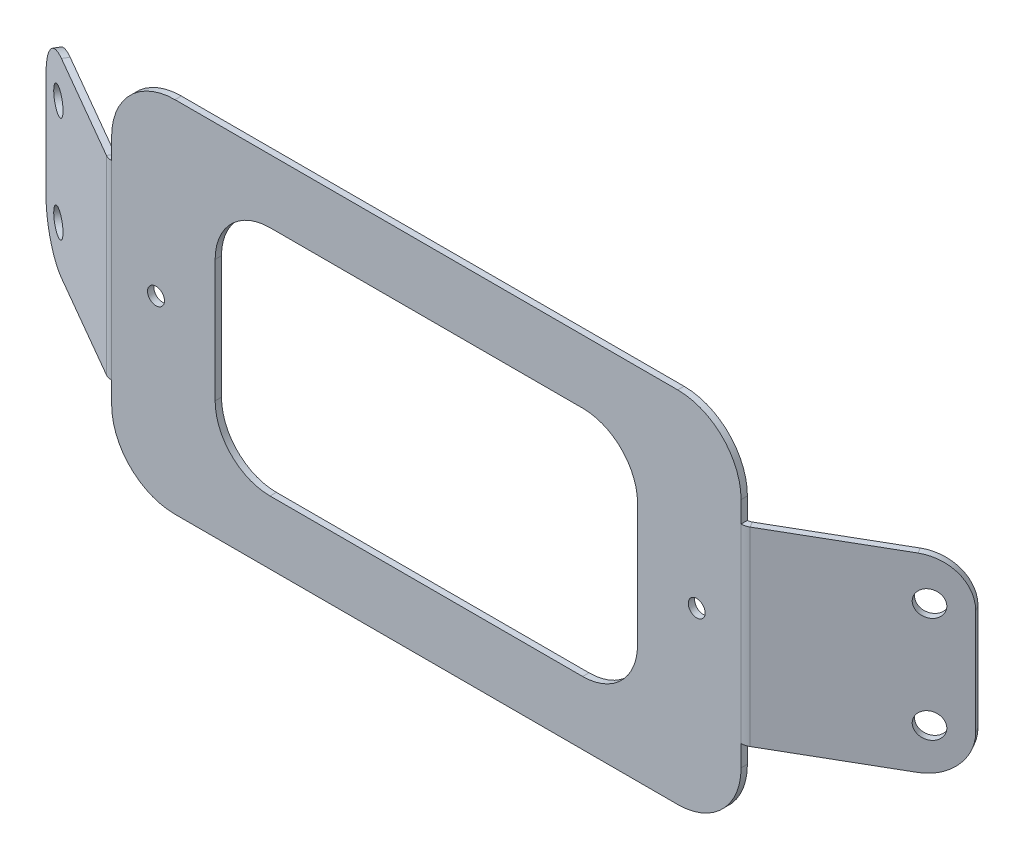
SolidWorks part; units mm, degrees
note: The reader was unsure of these and kept them because the rebuilt part matched: flange length of "Ребро-кромка1".
ref_plane "Спереди" through (0, 0, 0) normal (0, 0, 1) x (1, 0, 0)
ref_plane "Сверху" through (0, 0, 0) normal (0, 1, 0) x (1, 0, 0)
ref_plane "Справа" through (0, 0, 0) normal (1, 0, 0) x (0, 0, -1)
sketch "Sketch1" plane through (0, 0, 0) normal (0, 0, 1) x (1, 0, 0)
  line L1 (15, 0) -> (134, 0)
  line L2 (0, 15) -> (0, 70)
  line L3 (15, 85) -> (134, 85)
  line L4 (149, 15) -> (149, 70)
  line L9 (111.5, 15) -> (37.5, 15)
  line L10 (124.5, 28) -> (124.5, 57)
  line L11 (111.5, 70) -> (37.5, 70)
  line L12 (24.5, 28) -> (24.5, 57)
  arc A4 (37.5, 70) -> (24.5, 57) centre (37.5, 57) ccw
  arc A5 (37.5, 15) -> (24.5, 28) centre (37.5, 28) cw
  arc A6 (124.5, 57) -> (111.5, 70) centre (111.5, 57) ccw
  arc A7 (111.5, 15) -> (124.5, 28) centre (111.5, 28) ccw
  arc A8 (0, 70) -> (15, 85) centre (15, 70) cw
  arc A9 (15, 0) -> (0, 15) centre (15, 15) cw
  arc A10 (134, 85) -> (149, 70) centre (134, 70) cw
  arc A11 (134, 0) -> (149, 15) centre (134, 15) ccw
  point P13 (24.5, 15)
  point P16 (124.5, 70)
  point P19 (124.5, 15)
  point P22 (0, 85)
  point P25 (0, 0)
  point P30 (149, 0)
  dimension "D4" = 100
  dimension "D7" = 13
  dimension "D8" = 15
  dimension "D1" = 149
  dimension "D2" = 85
  dimension "D5" = 24.5
  dimension "D3" = 55
  dimension "D6" = 15
base flange "Base-Flange1" sketch "Sketch1" thickness 1.5 reverse thickness direction no parameters "D1"=1.85
edge flange "Ребро-кромка1" sketch "Sketch10" flange profiles "Sketch10", "Sketch11" flange angle 150 flange length 40 flange position bend outside bend radius 1.85 thickness 1.5 relief rectangular parameters "D6"=10, "D8"=1
sketch "Sketch10" plane through (0, 0, -1.5) normal (0.5, 0, -0.866) x (0, -1, 0)
  line L3 (-65, 39.5981) -> (-20, 39.5981)
  line L5 (-15, 0) -> (-70, 0) construction
  line L6 (-20, 0) -> (-65, 0)
  line L7 (-65, 0) -> (-65, 39.5981)
  line L8 (-20, 0) -> (-20, 39.5981)
sketch "Sketch11" plane through (149, 0, -1.5) normal (-0.5, 0, -0.866) x (0, 1, 0)
  line L0 (70, 0) -> (15, 0) construction
  line L1 (65, 0) -> (20, 0)
  line L3 (65, 39.5981) -> (20, 39.5981)
  line L5 (20, 0) -> (20, 39.5981)
  line L7 (65, 0) -> (65, 39.5981)
bend "EdgeBend1" bend radius 1.85 bend angle 30 parameters "D5"=1
bend "EdgeBend2" bend radius 1.85 bend angle 30 parameters "D5"=2
sketch "Sketch12" plane through (37.4744, 0, 64.9076) normal (0.5, 0, 0.866) x (0.866, 0, -0.5)
  line L0 (169.8152, 65) -> (169.8152, 20) construction
  line L1 (169.8152, 20) -> (130.7128, 20) construction
  line L2 (130.7128, 65) -> (169.8152, 65) construction
  circle A0 centre (161.8152, 30) radius 3
  circle A1 centre (161.8152, 55) radius 3
  dimension "D1" = 6
  dimension "D2" = 8
  dimension "D3" = 10
  dimension "D5" = 10
  dimension "D4" = 2
extrude "Cut-Extrude1" cut sketch "Sketch12" against normal blind 10 normal cut yes
fillet "Fillet1" radius 10 4 edges at (184.1636, 20, -20.6495) (184.1636, 65, -20.6495) (-35.1636, 20, -20.6495) (-35.1636, 65, -20.6495)
sketch "Sketch13" plane through (-0.2244, 0, 0.3887) normal (-0.5, 0, 0.866) x (0.866, 0, 0.5)
  line L0 (-1.675, 20) -> (-30.7774, 20) construction
  line L1 (-40.7774, 30) -> (-40.7774, 55) construction
  line L2 (-30.7774, 65) -> (-1.675, 65) construction
  circle A0 centre (-32.7774, 30) radius 3
  circle A1 centre (-32.7774, 55) radius 3
  dimension "D1" = 6
  dimension "D2" = 10
  dimension "D3" = 8
  dimension "D5" = 10
  dimension "D4" = 2
extrude "Cut-Extrude2" cut sketch "Sketch13" against normal blind 10 normal cut yes
sketch "Sketch14" plane through (0, 0, -1.5) normal (0, 0, -1) x (-1, 0, 0)
  line L1 (-74.5, 0) -> (-74.5, 85) construction
  line L3 (-15, 0) -> (-134, 0) construction
  line L4 (-124.5, 28) -> (-124.5, 57) construction
  line L6 (-134, 85) -> (-15, 85) construction
  circle A2 centre (-138.5, 42.5) radius 2
  circle A3 centre (-10.5, 42.5) radius 2
  dimension "D1" = 4
  dimension "D2" = 42.5
  dimension "D3" = 14
extrude "Cut-Extrude3" cut sketch "Sketch14" against normal blind 10 normal cut yes
sketch "Сгиб-Линии1" plane through (0, 0, 0) normal (0, 1, 0) x (1, 0, 0)
sketch "Граничная рамка1" plane through (0, 0, 0) normal (0, 1, 0) x (1, 0, 0)
sheet metal parameters "Листовой металл3" thickness 1.5 parameters "D1"=1.85
flat pattern "Развертка3" [suppressed]
sketch "Сгиб-Линии2" plane through (0, 0, 0) normal (0, 1, 0) x (1, 0, 0)
sketch "Граничная рамка2" [suppressed] plane through (0, 0, 0) normal (0, 1, 0) x (1, 0, 0)
sheet metal parameters "Листовой металл4" thickness 1.5 parameters "D1"=1.85
flat pattern "Развертка3" [suppressed]
sketch "Сгиб-Линии2" plane through (0, 0, 0) normal (0, 1, 0) x (1, 0, 0)
sketch "Граничная рамка2" [suppressed] plane through (0, 0, 0) normal (0, 1, 0) x (1, 0, 0)
bend of the flat pattern "Плоское состояние-<EdgeBend1>1"
bend of the flat pattern "Плоское состояние-<EdgeBend2>1"
sheet metal parameters "Листовой металл5" thickness 1.5 parameters "D1"=1.85
flat pattern "Развертка3" [suppressed]
sketch "Сгиб-Линии2" plane through (0, 0, 0) normal (0, 1, 0) x (1, 0, 0)
sketch "Граничная рамка2" [suppressed] plane through (0, 0, 0) normal (0, 1, 0) x (1, 0, 0)
bend of the flat pattern "Плоское состояние-<EdgeBend1>1"
bend of the flat pattern "Плоское состояние-<EdgeBend2>1"
sheet metal parameters "Листовой металл6" thickness 1.5 parameters "D1"=1.85
flat pattern "Развертка3" [suppressed]
sketch "Сгиб-Линии2" plane through (0, 0, 0) normal (0, 1, 0) x (1, 0, 0)
sketch "Граничная рамка2" [suppressed] plane through (0, 0, 0) normal (0, 1, 0) x (1, 0, 0)
bend of the flat pattern "Плоское состояние-<EdgeBend1>1"
bend of the flat pattern "Плоское состояние-<EdgeBend2>1"
sheet metal parameters "Листовой металл8" thickness 1.5 parameters "D1"=1.85
flat pattern "Развертка3" [suppressed]
sketch "Сгиб-Линии2" plane through (0, 0, 0) normal (0, 1, 0) x (1, 0, 0)
sketch "Граничная рамка2" [suppressed] plane through (0, 0, 0) normal (0, 1, 0) x (1, 0, 0)
bend of the flat pattern "Плоское состояние-<EdgeBend1>1"
bend of the flat pattern "Плоское состояние-<EdgeBend2>1"
